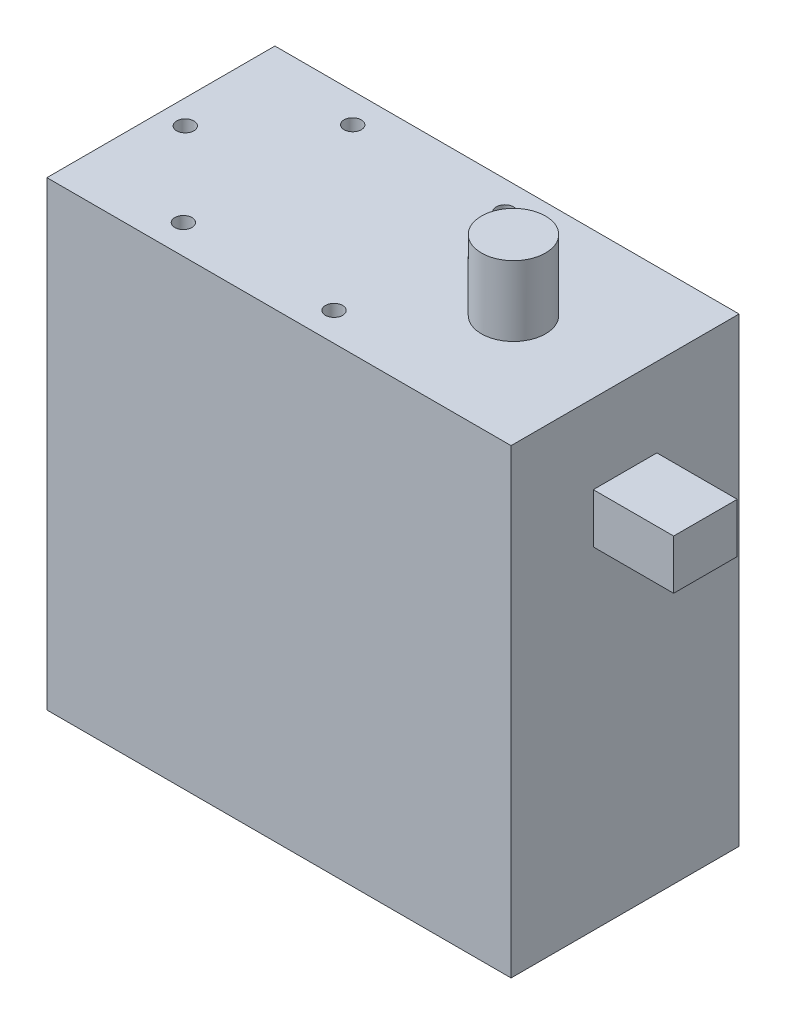
SolidWorks part; units mm, degrees
ref_plane "Front Plane" through (0, 0, 0) normal (0, 0, 1) x (1, 0, 0)
ref_plane "Top Plane" through (0, 0, 0) normal (0, 1, 0) x (1, 0, 0)
ref_plane "Right Plane" through (0, 0, 0) normal (1, 0, 0) x (0, 0, -1)
sketch "Sketch1" plane through (0, 0, 0) normal (0, 0, 1) x (1, 0, 0)
  line L1 (0, 0) -> (40.43, 0)
  line L2 (0, 0) -> (0, 40.16)
  line L3 (0, 40.16) -> (40.43, 40.16)
  line L4 (40.43, 0) -> (40.43, 40.16)
  dimension "D1" = 40.16
  dimension "D2" = 40.43
extrude "ServoBody" add sketch "Sketch1" along normal blind 19.86
sketch "Sketch2" plane through (0, 40.16, 0) normal (0, 1, 0) x (1, 0, 0)
  line L0 (40.43, -19.86) -> (40.43, 0) construction
  circle A0 centre (30.71, -9.93) radius 2.79
  point P5 (40.43, -9.93)
  dimension "D1" = 5.58
  dimension "D2" = 9.72
extrude "GearHinge" add sketch "Sketch2" along normal blind 6.1
sketch "Sketch3" plane through (0, 0, 0) normal (0, -1, 0) x (1, 0, 0)
  circle A0 centre (30.71, 9.93) radius 3.01
  circle A1 centre (30.71, 9.93) radius 2.79 construction
  dimension "D1" = 6.02
extrude "SmoothHinge" add sketch "Sketch3" along normal blind 5.5
sketch "Sketch4" plane through (0, 40.16, 0) normal (0, 1, 0) x (1, 0, 0)
  line L3 (0, -19.86) -> (0, 0) construction
  circle A0 centre (22.52, -2.49) radius 0.75
  circle A4 centre (22.52, -17.37) radius 0.75
  circle A5 centre (2.12, -9.93) radius 0.75
  circle A6 centre (9.33, -2.555) radius 0.75
  circle A7 centre (9.33, -17.305) radius 0.75
  point P21 (0, -9.93)
  dimension "D1" = 1.5
  dimension "D8" = 2.12
  dimension "D6" = 14.75
  dimension "D5" = 7.375
  dimension "D2" = 22.52
  dimension "D3" = 14.88
  dimension "D4" = 7.44
  dimension "D7" = 7.21
extrude "GearScrewHoles" cut sketch "Sketch4" against normal blind 2
sketch "Sketch5" plane through (0, 0, 0) normal (0, -1, 0) x (1, 0, 0)
  line L2 (0, 19.86) -> (0, 0) construction
  circle A0 centre (17.5, 17.92) radius 0.75
  circle A1 centre (38.62, 17.92) radius 0.75
  circle A2 centre (2.3, 17.92) radius 0.75
  circle A3 centre (17.5, 1.94) radius 0.75
  circle A4 centre (38.62, 1.94) radius 0.75
  circle A5 centre (2.3, 1.94) radius 0.75
  point P14 (0, 9.93)
  dimension "D1" = 1.5
  dimension "D2" = 21.12
  dimension "D3" = 15.98
  dimension "D4" = 7.99
  dimension "D5" = 15.2
  dimension "D6" = 2.3
extrude "SmoothScrewHoles" cut sketch "Sketch5" against normal blind 2
sketch "Sketch6" plane through (40.43, 0, 0) normal (1, 0, 0) x (0, 0, -1)
  line L0 (-19.86, 40.16) -> (0, 40.16) construction
  line L1 (-12.7, 33.26) -> (-7.16, 33.26)
  line L2 (-12.7, 33.26) -> (-12.7, 28.94)
  line L3 (-12.7, 28.94) -> (-7.16, 28.94)
  line L4 (-7.16, 33.26) -> (-7.16, 28.94)
  point P6 (-9.93, 33.26)
  point P7 (-9.93, 40.16)
  dimension "D1" = 6.9
  dimension "D2" = 5.54
  dimension "D3" = 4.32
extrude "Cable" add sketch "Sketch6" along normal blind 7
equation "\"D5@Sketch4\"=\"D6@Sketch4\"/2"
equation "\"D4@Sketch4\"=\"D3@Sketch4\"/2"
